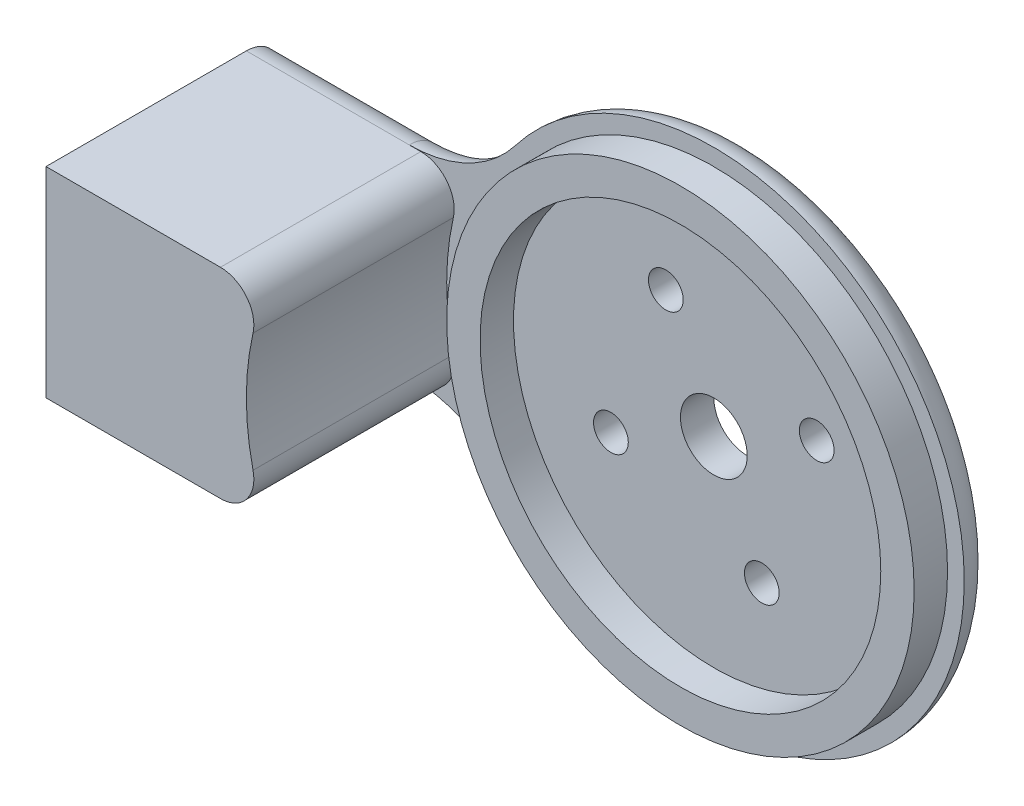
SolidWorks part; units mm, degrees
ref_plane "Plan de face" through (0, 0, 0) normal (0, 0, 1) x (1, 0, 0)
ref_plane "Plan de dessus" through (0, 0, 0) normal (0, 1, 0) x (1, 0, 0)
ref_plane "Plan de droite" through (0, 0, 0) normal (1, 0, 0) x (0, 0, -1)
sketch "Esquisse1" plane through (0, 0, 0) normal (0, 0, 1) x (1, 0, 0)
  line L0 (-1000, 0) -> (49000, 0) construction
  line L1 (-45.6207, 15) -> (-70, 15)
  line L4 (-70, -15) -> (-70, 15)
  line L5 (-45.6207, -15) -> (-70, -15)
  arc A0 (-29.7526, -22.8261) -> (-29.7526, 22.8261) centre (0, 0) ccw
  circle A1 centre (0, 0) radius 5
  arc A2 (-45.6207, 15) -> (-29.7526, 22.8261) centre (-45.6207, 35) ccw
  arc A3 (-45.6207, -15) -> (-29.7526, -22.8261) centre (-45.6207, -35) cw
  point P8 (-34.3693, -15)
  point P9 (-70, 0)
  point P13 (-70, 0)
  point P20 (-34.3693, 15)
  dimension "D1" = 75
  dimension "D4" = 10
  dimension "D5" = 20
  dimension "D2" = 15
  dimension "D3" = 70
extrude "Boss.-Extru.1" add sketch "Esquisse1" along normal blind 5
sketch "Esquisse6" plane through (0, 0, 5) normal (0, 0, 1) x (1, 0, 0)
  circle A0 centre (0, 0) radius 35
  circle A1 centre (0, 0) radius 30
  dimension "D1" = 70
  dimension "D2" = 60
extrude "Boss.-Extru.6" add sketch "Esquisse6" along normal blind 5
sketch "Esquisse8" plane through (0, 0, 5) normal (0, 0, 1) x (1, 0, 0)
  line L1 (-1000, 0) -> (49000, 0) construction
  line L3 (-70, -15) -> (-70, 15)
  line L9 (-70, -15) -> (-43.8748, -15)
  line L10 (-70, 15) -> (-43.8748, 15)
  line L20 (-70, 15) -> (-70, -15) construction
  arc A2 (-38.9998, 8.8889) -> (-38.9998, -8.8889) centre (0, 0) ccw
  arc A3 (-43.8748, 15) -> (-38.9998, 8.8889) centre (-43.8748, 10) cw
  arc A4 (-43.8748, -15) -> (-38.9998, -8.8889) centre (-43.8748, -10) ccw
  point P5 (-70, 0)
  point P15 (-70, 0)
  dimension "D1" = 80
  dimension "D2" = 5
extrude "Boss.-Extru.9" add sketch "Esquisse8" along normal blind 30
fillet "Congé3" radius 5 5 edges at (37.5, 0, 0) (-57.8104, 15, 0) (-57.8104, -15, 0) (-36.7742, -17.0629, 0) (-36.7742, 17.0629, 0)
sketch "Esquisse10" plane through (0, 0, 0) normal (0, 0, -1) x (-1, 0, 0)
  line L0 (-1000, 0) -> (49000, 0) construction
  line L1 (0, 0) -> (-32712.2105, 15253.9543) construction
  circle A0 centre (-15.4072, 7.1845) radius 2.6
  circle A1 centre (7.1845, 15.4072) radius 2.6
  circle A2 centre (15.4072, -7.1845) radius 2.6
  circle A3 centre (-7.1845, -15.4072) radius 2.6
  point P15 (0, 0)
  dimension "D2" = 5.2
  dimension "D1" = 25
  dimension "D3" = 17
  dimension "D4" = 4
extrude "Enlèv. mat.-Extru.1" cut sketch "Esquisse10" against normal through all
